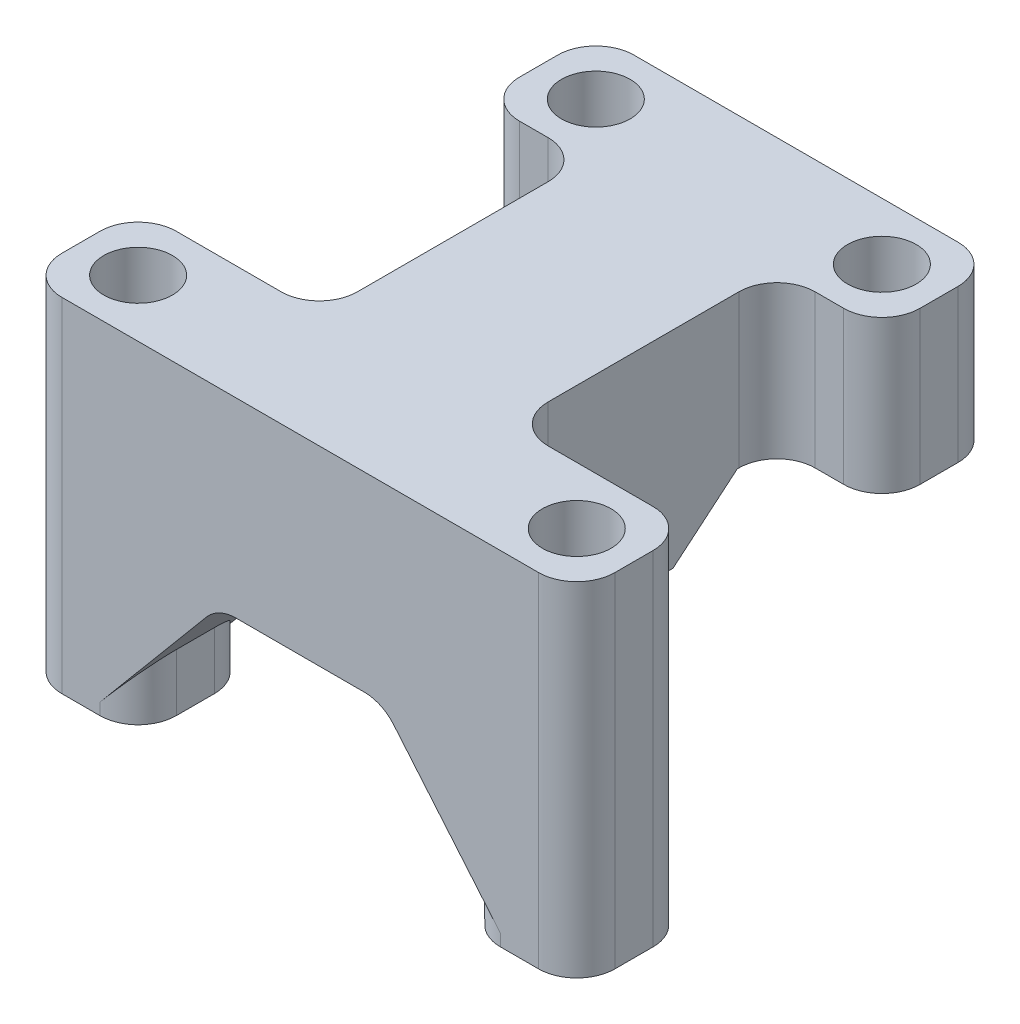
SolidWorks part; units mm, degrees
ref_plane "Front Plane" through (0, 0, 0) normal (0, 0, 1) x (1, 0, 0)
ref_plane "Top Plane" through (0, 0, 0) normal (0, 1, 0) x (1, 0, 0)
ref_plane "Right Plane" through (0, 0, 0) normal (1, 0, 0) x (0, 0, -1)
other "Configuration Table"
sketch "Sketch2" plane through (0, 0, 0) normal (0, 1, 0) x (1, 0, 0)
  line L0 (-11.5, 3) -> (-5, 3)
  line L1 (-11.5, -3) -> (11.5, -3)
  line L2 (-11.5, 0) -> (11.5, 0) construction
  line L3 (0, 0) -> (0, 20) construction
  line L4 (-7.5, 20) -> (7.5, 20) construction
  line L5 (-7.5, 23) -> (7.5, 23)
  line L6 (-7.5, 17) -> (-5, 17)
  line L7 (5, 3) -> (5, 17)
  line L8 (-5, 3) -> (-5, 17)
  line L9 (-5, 0) -> (-5, 20) construction
  line L10 (5, 0) -> (5, 20) construction
  line L11 (-5, 17) -> (0, 17) construction
  line L12 (5, 17) -> (7.5, 17)
  line L13 (0, 17) -> (5, 17) construction
  line L14 (-5, 3) -> (0, 3) construction
  line L15 (5, 3) -> (11.5, 3)
  line L16 (0, 3) -> (5, 3) construction
  line L17 (-11.5, 3) -> (-14.5, 3)
  line L18 (-14.5, 3) -> (-14.5, -3)
  line L20 (-14.5, -3) -> (-11.5, -3)
  line L21 (-7.5, 17) -> (-10.5, 17)
  line L22 (-10.5, 17) -> (-10.5, 23)
  line L23 (-10.5, 23) -> (-7.5, 23)
  line L24 (7.5, 23) -> (10.5, 23)
  line L25 (10.5, 23) -> (10.5, 17)
  line L26 (10.5, 17) -> (7.5, 17)
  line L27 (11.5, 3) -> (14.5, 3)
  line L28 (14.5, 3) -> (14.5, -3)
  line L29 (14.5, -3) -> (11.5, -3)
  circle A0 centre (-11.5, 0) radius 1.8
  circle A1 centre (11.5, 0) radius 1.8
  arc A2 (-11.5, 3) -> (-14.5, 0) centre (-11.5, 0) ccw construction
  arc A3 (11.5, -3) -> (14.5, 0) centre (11.5, 0) ccw construction
  arc A4 (-11.5, -3) -> (-11.5, 3) centre (-11.5, 0) ccw construction
  arc A5 (11.5, 3) -> (11.5, -3) centre (11.5, 0) ccw construction
  circle A6 centre (-7.5, 20) radius 1.8
  circle A7 centre (7.5, 20) radius 1.8
  arc A8 (-7.5, 23) -> (-10.5, 20) centre (-7.5, 20) ccw construction
  arc A9 (7.5, 17) -> (10.5, 20) centre (7.5, 20) ccw construction
  arc A10 (-7.5, 17) -> (-4.5, 20) centre (-7.5, 20) ccw construction
  arc A11 (-4.5, 20) -> (-7.5, 23) centre (-7.5, 20) ccw construction
  arc A12 (7.5, 23) -> (4.5, 20) centre (7.5, 20) ccw construction
  arc A13 (4.5, 20) -> (7.5, 17) centre (7.5, 20) ccw construction
  arc A14 (-10.5, 20) -> (-7.5, 17) centre (-7.5, 20) ccw construction
  arc A15 (10.5, 20) -> (7.5, 23) centre (7.5, 20) ccw construction
  arc A16 (14.5, 0) -> (11.5, 3) centre (11.5, 0) ccw construction
  arc A17 (-14.5, 0) -> (-11.5, -3) centre (-11.5, 0) ccw construction
  dimension "D2" = 3.6
  dimension "D3" = 6
  dimension "D4" = 20
  dimension "D5" = 15
  dimension "D6" = 5
  dimension "D1" = 23
  dimension "D7" = 5
extrude "Boss-Extrude1" add sketch "Sketch2" against normal blind 10
chamfer "Chamfer1" distance 20 angle 40 1 edges at (0, -10, -23) first distance on face at (7.5, -10, -18.2)
sketch "Sketch4" plane through (0, 0, 0) normal (0, 1, 0) x (1, 0, 0)
  line L0 (-7.5, 23) -> (7.5, 23) construction
  line L1 (-10.5, 23) -> (-7.5, 23) construction
  line L2 (-10.5, 17) -> (-10.5, 23) construction
  line L3 (-7.5, 17) -> (-10.5, 17) construction
  line L4 (-7.5, 17) -> (-5, 17) construction
  line L5 (-5, 3) -> (-5, 17) construction
  line L6 (-11.5, 3) -> (-14.5, 3) construction
  line L7 (-11.5, 3) -> (-5, 3) construction
  line L8 (-14.5, 3) -> (-14.5, -3) construction
  line L9 (-14.5, -3) -> (-11.5, -3) construction
  line L10 (-11.5, -3) -> (11.5, -3) construction
  line L11 (-7.5, 23) -> (7.5, 23)
  line L12 (-10.5, 23) -> (-7.5, 23)
  line L13 (-10.5, 17) -> (-10.5, 23)
  line L14 (-7.5, 17) -> (-10.5, 17)
  line L15 (-7.5, 17) -> (-5, 17)
  line L16 (-5, 3) -> (-5, 17)
  line L17 (-11.5, 3) -> (-14.5, 3)
  line L18 (-11.5, 3) -> (-5, 3)
  line L19 (-14.5, 3) -> (-14.5, -3)
  line L20 (-14.5, -3) -> (-11.5, -3)
  line L21 (-11.5, -3) -> (11.5, -3)
  line L22 (7.5, 23) -> (10.5, 23) construction
  line L23 (10.5, 23) -> (10.5, 17) construction
  line L24 (5, 17) -> (7.5, 17) construction
  line L25 (10.5, 17) -> (7.5, 17) construction
  line L26 (5, 3) -> (5, 17) construction
  line L27 (5, 3) -> (11.5, 3) construction
  line L28 (11.5, 3) -> (14.5, 3) construction
  line L29 (14.5, 3) -> (14.5, -3) construction
  line L30 (14.5, -3) -> (11.5, -3) construction
  line L31 (7.5, 23) -> (10.5, 23)
  line L32 (10.5, 23) -> (10.5, 17)
  line L33 (5, 17) -> (7.5, 17)
  line L34 (10.5, 17) -> (7.5, 17)
  line L35 (5, 3) -> (5, 17)
  line L36 (5, 3) -> (11.5, 3)
  line L37 (11.5, 3) -> (14.5, 3)
  line L38 (14.5, 3) -> (14.5, -3)
  line L39 (14.5, -3) -> (11.5, -3)
  circle A0 centre (-11.5, 0) radius 1.8 construction
  circle A1 centre (11.5, 0) radius 1.8 construction
  circle A2 centre (7.5, 20) radius 1.8 construction
  circle A3 centre (-7.5, 20) radius 1.8 construction
  circle A4 centre (-11.5, 0) radius 1.8
  circle A5 centre (11.5, 0) radius 1.8
  circle A6 centre (7.5, 20) radius 1.8
  circle A7 centre (-7.5, 20) radius 1.8
extrude "Boss-Extrude3" add sketch "Sketch4" along normal blind 8
chamfer "Chamfer2" [suppressed] distance 20 angle 40
sketch "Sketch5" plane through (0, -10, 0) normal (0, -1, 0) x (1, 0, 0)
  line L0 (-14.5, 3) -> (14.5, 3) construction
  line L1 (-8.5, 3) -> (8.5, 3)
  line L2 (-8.5, 3) -> (-8.5, -3)
  line L3 (-8.5, -3) -> (8.5, -3) construction
  line L4 (8.5, 3) -> (8.5, -3)
  line L5 (14.5, -3) -> (5, -3) construction
  line L6 (-8.5, -3) -> (-8.5, -14.9175)
  line L7 (8.5, -3) -> (8.5, -14.9175)
  line L8 (8.5, -14.9175) -> (5, -14.9175)
  line L9 (-5, -14.9175) -> (-8.5, -14.9175)
  line L10 (5, -14.9175) -> (-5, -14.9175) construction
  line L11 (5, -14.9175) -> (-5, -14.9175)
  circle A0 centre (-11.5, 0) radius 1.8 construction
  circle A1 centre (11.5, 0) radius 1.8 construction
  dimension "D1" = 3
  dimension "D2" = 3
extrude "Cut-Extrude1" cut sketch "Sketch5" against normal blind 8
chamfer "Chamfer3" distance 5 angle 40 2 edges at (8.5, -2, 0) (-8.5, -2, 0) first distance on face at (8.5, -6, 0) first distance on face at (-8.5, -6, 0)
fillet "Fillet1" radius 2 18 edges at (5, 4, -17) (-5, 4, -17) (-5, 2.5856, -3) (14.5, -1, 3) (5, 2.5856, -3) (14.5, -1, -3) (10.5, 4, -17) (10.5, 4, -23) (-10.5, 4, -17) (-10.5, 4, -23) (-14.5, -1, 3) (-14.5, -1, -3) (8.5, -8.5, 3) (8.5, -8.5, -3) (-8.5, -8.5, -3) (-8.5, -8.5, 3) (4.3045, -2, -4.767) (-4.3045, -2, -4.767)
